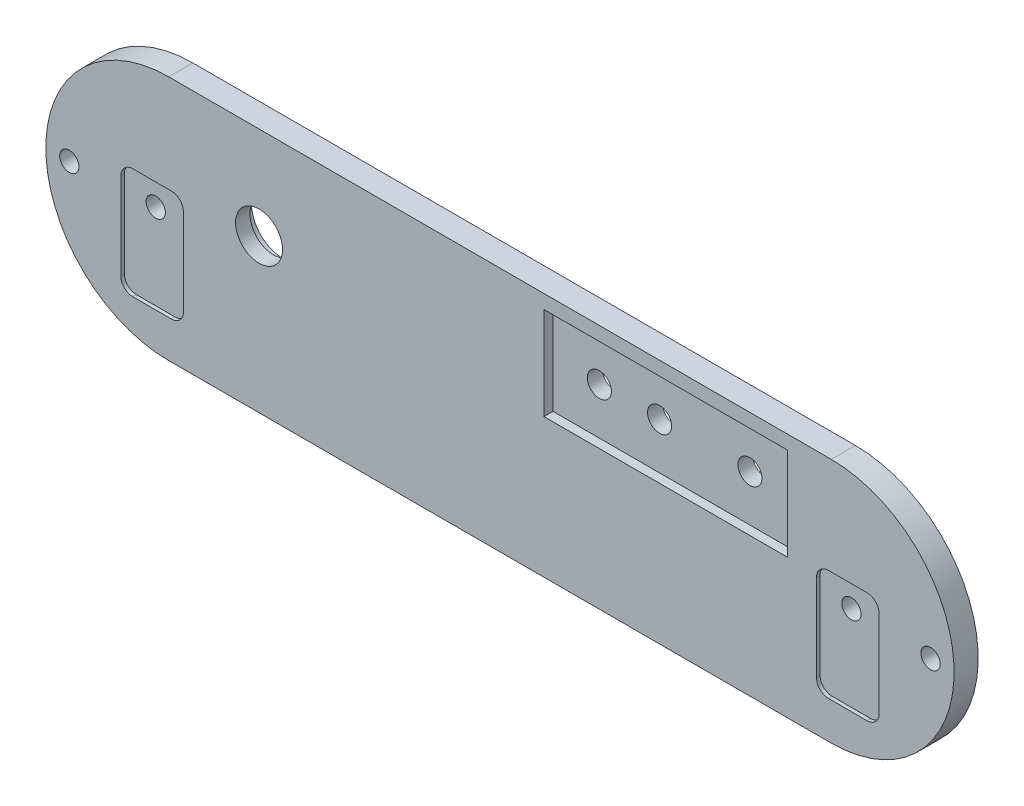
SolidWorks part; units mm, degrees
ref_plane "Plan de face" through (0, 0, 0) normal (0, 0, 1) x (1, 0, 0)
ref_plane "Plan de dessus" through (0, 0, 0) normal (0, 1, 0) x (1, 0, 0)
ref_plane "Plan de droite" through (0, 0, 0) normal (1, 0, 0) x (0, 0, -1)
sketch "Esquisse1" plane through (0, 0, 0) normal (0, 0, 1) x (1, 0, 0)
  line L0 (-55, 0) -> (55, 0) construction
  line L1 (-55, 22.5) -> (55, 22.5) construction
  line L2 (-55, -22.5) -> (55, -22.5) construction
  line L3 (-55, 20.4) -> (55, 20.4)
  line L4 (-55, -20.4) -> (55, -20.4)
  arc A0 (-55, 22.5) -> (-55, -22.5) centre (-55, 0) ccw construction
  arc A1 (55, -22.5) -> (55, 22.5) centre (55, 0) ccw construction
  arc A2 (55, -20.4) -> (55, 20.4) centre (55, 0) ccw
  arc A3 (-55, 20.4) -> (-55, -20.4) centre (-55, 0) ccw
  point P2 (0, 0)
  dimension "D1" = 110
  dimension "D2" = 45
  dimension "D3" = 2.1
extrude "Boss.-Extru.1" add sketch "Esquisse1" along normal blind 4
sketch "Esquisse6" plane through (0, 0, 4) normal (0, 0, 1) x (1, 0, 0)
  line L0 (71.5, 0) -> (-71.5, 0) construction
  line L1 (-57.75, 0) -> (57.75, 0) construction
  circle A0 centre (-57.75, 0) radius 1.6
  circle A1 centre (57.75, 0) radius 1.6
  circle A2 centre (71.5, 0) radius 1.6
  circle A3 centre (-71.5, 0) radius 1.6
  point P6 (0, 0)
  dimension "D1" = 3.2
  dimension "D2" = 115.5
  dimension "D3" = 143
extrude "Enlèv. mat.-Extru.3" cut sketch "Esquisse6" against normal through all
sketch "Esquisse7" plane through (0, 0, 4) normal (0, 0, 1) x (1, 0, 0)
  line L1 (-62.75, 4) -> (-52.75, 4) construction
  line L2 (-62.75, 4) -> (-62.75, -14) construction
  line L3 (-62.75, -14) -> (-52.75, -14) construction
  line L4 (-52.75, 4) -> (-52.75, -14) construction
  line L5 (-60.95, 4.2) -> (-54.55, 4.2)
  line L6 (-52.55, 2.2) -> (-52.55, -12.2)
  line L7 (-60.95, -14.2) -> (-54.55, -14.2)
  line L8 (-62.95, 2.2) -> (-62.95, -12.2)
  line L9 (-62.95, 4.2) -> (-62.95, -14.2) construction
  line L10 (-62.95, -14.2) -> (-52.55, -14.2) construction
  line L11 (-52.55, 4.2) -> (-52.55, -14.2) construction
  line L12 (-62.95, 4.2) -> (-52.55, 4.2) construction
  line L13 (0, -2.2) -> (0, 2.2) construction
  line L14 (60.95, 4.2) -> (54.55, 4.2)
  line L15 (52.55, 2.2) -> (52.55, -12.2)
  line L16 (60.95, -14.2) -> (54.55, -14.2)
  line L17 (62.95, 2.2) -> (62.95, -12.2)
  arc A1 (-62.95, -12.2) -> (-60.95, -14.2) centre (-60.95, -12.2) ccw
  arc A2 (-52.55, -12.2) -> (-54.55, -14.2) centre (-54.55, -12.2) cw
  arc A3 (-54.55, 4.2) -> (-52.55, 2.2) centre (-54.55, 2.2) cw
  arc A4 (-60.95, 4.2) -> (-62.95, 2.2) centre (-60.95, 2.2) ccw
  arc A5 (60.95, 4.2) -> (62.95, 2.2) centre (60.95, 2.2) cw
  arc A6 (54.55, 4.2) -> (52.55, 2.2) centre (54.55, 2.2) ccw
  arc A7 (52.55, -12.2) -> (54.55, -14.2) centre (54.55, -12.2) ccw
  arc A8 (62.95, -12.2) -> (60.95, -14.2) centre (60.95, -12.2) cw
  circle A9 centre (-57.75, 0) radius 1.6 construction
  dimension "D5" = 2
  dimension "D1" = 10
  dimension "D2" = 18
  dimension "D3" = 4
  dimension "D4" = 0.2
  dimension "D6" = 5
extrude "Enlèv. mat.-Extru.4" cut sketch "Esquisse7" against normal blind 0.6
sketch "Esquisse8" plane through (0, 0, 4) normal (0, 0, 1) x (1, 0, 0)
  line L0 (7.3, 10.4) -> (15, 10.4) construction
  line L1 (7.3, 18.1) -> (47.7, 18.1)
  line L2 (7.3, 18.1) -> (7.3, 2.7)
  line L3 (7.3, 2.7) -> (47.7, 2.7)
  line L4 (47.7, 18.1) -> (47.7, 2.7)
  line L5 (15, 10.4) -> (25, 10.4) construction
  line L6 (25, 10.4) -> (40, 10.4) construction
  line L7 (40, 10.4) -> (47.7, 10.4) construction
  line L8 (55, 20.4) -> (-55, 20.4) construction
  circle A0 centre (25, 10.4) radius 2
  circle A1 centre (15, 10.4) radius 2
  circle A2 centre (40, 10.4) radius 2
  dimension "D4" = 4
  dimension "D1" = 7.7
  dimension "D2" = 15.4
  dimension "D3" = 10
  dimension "D5" = 10
  dimension "D6" = 25
  dimension "D7" = 15
extrude "Enlèv. mat.-Extru.5" cut sketch "Esquisse8" against normal offset from surface (1.5 mm away) 2.5 contours L1 L4 L3 L2 up to face at (73.1, 0, 0)
extrude "Enlèv. mat.-Extru.6" cut sketch "Esquisse8<3>" against normal through all contours A1 | A0 | A2
sketch "Esquisse8<3>" plane through (0, 0, 4) normal (0, 0, 1) x (1, 0, 0) same geometry as "Esquisse8"
sketch "Esquisse9" plane through (0, 0, 0) normal (0, 0, -1) x (-1, 0, 0)
  circle A0 centre (40, 5) radius 5.25
  circle A1 centre (40, 5) radius 3.9
  dimension "D1" = 10.5
  dimension "D2" = 7.8
  dimension "D3" = 5
  dimension "D4" = 40
extrude "Enlèv. mat.-Extru.7" cut sketch "Esquisse9" against normal blind 1.6 contours A0
extrude "Enlèv. mat.-Extru.8" cut sketch "Esquisse9<3>" against normal through all contours A1
sketch "Esquisse9<3>" plane through (0, 0, 0) normal (0, 0, -1) x (-1, 0, 0) same geometry as "Esquisse9"
sketch "Esquisse10" plane through (0, 0, 0) normal (0, 0, -1) x (-1, 0, 0)
  line L0 (-40, 10.4) -> (-42.1213, 8.2787) construction
  line L1 (-17.1213, 8.2787) -> (11.5574, -20.4) construction
  line L2 (30.5003, -7) -> (49.4997, -7) construction
  line L3 (-27.1213, 8.2787) -> (1.5574, -20.4) construction
  line L4 (55, -20.4) -> (-55, -20.4) construction
  line L5 (-42.1213, 8.2787) -> (-13.4426, -20.4) construction
  line L6 (-27.1213, 8.2787) -> (-25, 10.4) construction
  line L7 (40, 5) -> (40, -7) construction
  line L8 (-15, 10.4) -> (-17.1213, 8.2787) construction
  text T0 "   HOURS" font "Anurati" height 5
  text T1 "   MI NUTES" font "Anurati" height 5
  text T2 "   LI GHTS" font "Anurati" height 5
  text T3 "5V" height 4
  point P13 (40, -7)
  point P15 (40, -7.5177)
  point P16 (49.4997, -7.5491)
  dimension "D1" = 3
  dimension "D2" = 45
  dimension "D3" = 12
extrude "Enlèv. mat.-Extru.9" cut sketch "Esquisse10" against normal blind 0.8
